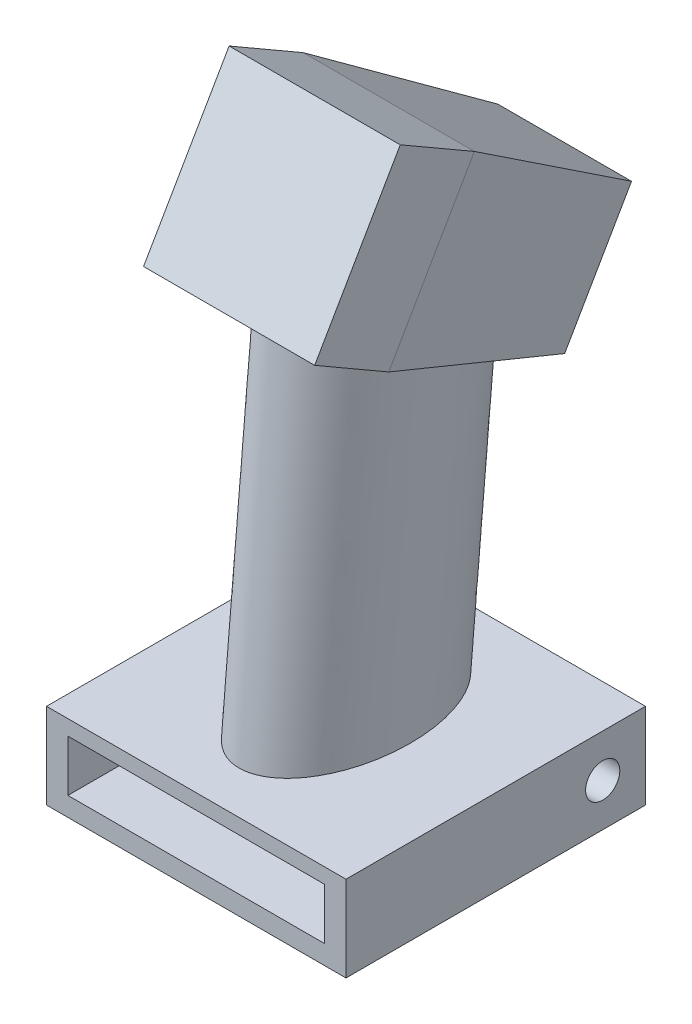
SolidWorks part; units mm, degrees
ref_plane "Front Plane" through (0, 0, 0) normal (0, 0, 1) x (1, 0, 0)
ref_plane "Top Plane" through (0, 0, 0) normal (0, 1, 0) x (1, 0, 0)
ref_plane "Right Plane" through (0, 0, 0) normal (1, 0, 0) x (0, 0, -1)
sketch "Sketch2" plane through (0, 0, 0) normal (0, 1, 0) x (1, 0, 0)
  line L0 (0, 0) -> (0, 35.7242) construction
  line L1 (0, 0) -> (12.5, 0) construction
  ellipse E0 centre (0, 0) end of major axis (0, -25) minor radius 15
  ellipse E1 centre (0, 0) end of major axis (0, 22.5) minor radius 12.5
  dimension "D1" = 12.5
  dimension "D2" = 15
  dimension "D3" = 22.5
  dimension "D4" = 25
sketch "Sketch3" plane through (0, 0, 0) normal (1, 0, 0) x (0, 0, -1)
  line L0 (0, 0) -> (5.118, 58.4992) construction
  line L1 (25, 0) -> (-25, 0) construction
  dimension "D1" = 85
extrude "Boss-Extrude1" add sketch "Sketch2" along direction (0, 0.9962, -0.0872) on the side of the normal blind 100
ref_axis "Axis1" through (0, 156.9007, 0) along (0, -1, 0)
ref_plane "Plane3" through (0, 100, 0) normal (0, 1, 0) x (1, 0, 0)
ref_axis "Axis4" through (16.5, 100, 0) along (-1, 0, 0)
ref_plane "Plane4" through (0, 25, 43.3013) normal (0, -0.5, -0.866) x (-1, 0, 0)
sketch "Sketch8" plane through (0, 25, 43.3013) normal (0, -0.5, -0.866) x (-1, 0, 0)
  line L0 (0, 135.88) -> (0, -6.4705) construction
  line L1 (-20, 66.6025) -> (20, 66.6025)
  line L2 (-20, 66.6025) -> (-20, 106.6025)
  line L3 (-20, 106.6025) -> (20, 106.6025)
  line L4 (20, 66.6025) -> (20, 106.6025)
  line L5 (-20, 66.6025) -> (20, 106.6025) construction
  line L6 (-20, 106.6025) -> (20, 66.6025) construction
  line L7 (-16.5, 86.6025) -> (16.5, 86.6025) construction
  point P0 (0, 86.6025)
  dimension "D1" = 40
  dimension "D2" = 40
extrude "Boss-Extrude2" add sketch "Sketch8" against normal blind 20 and the other way blind 50 draft 5 contours L1 L4 L3 L2
sketch "Sketch9" plane through (0, 0, 0) normal (0, -1, 0) x (-1, 0, 0)
  line L1 (35, 35) -> (-35, 35)
  line L2 (35, 35) -> (35, -35)
  line L3 (35, -35) -> (-35, -35)
  line L4 (-35, 35) -> (-35, -35)
  line L5 (35, 35) -> (-35, -35) construction
  line L6 (35, -35) -> (-35, 35) construction
  point P0 (0, 0)
  dimension "D1" = 70
  dimension "D2" = 70
extrude "Boss-Extrude3" add sketch "Sketch9" along normal blind 20
sketch "Sketch10" plane through (0, 0, 35) normal (0, 0, 1) x (1, 0, 0)
  line L0 (0, -9.5378) -> (0, 1.6534) construction
  line L1 (-30, -15.5378) -> (30, -15.5378)
  line L2 (-30, -15.5378) -> (-30, -3.5378)
  line L3 (-30, -3.5378) -> (30, -3.5378)
  line L4 (30, -15.5378) -> (30, -3.5378)
  line L5 (-30, -15.5378) -> (30, -3.5378) construction
  line L6 (-30, -3.5378) -> (30, -15.5378) construction
  line L7 (0, 0) -> (0, 58.4992) construction
  line L8 (0, -9.5378) -> (18.1969, -9.5378) construction
  point P0 (0, -9.5378)
  dimension "D1" = 12
  dimension "D2" = 60
extrude "Cut-Extrude1" cut sketch "Sketch10" against normal blind 55
sketch "Sketch11" plane through (35, 0, 0) normal (1, 0, 0) x (0, 0, -1)
  line L0 (35, -10) -> (58.9727, -10) construction
  line L2 (35, -20) -> (35, 0) construction
  circle A0 centre (25, -10) radius 1.75
  dimension "D2" = 3.5
  dimension "D1" = 10
extrude "Cut-Extrude2" cut sketch "Sketch11" against normal through all both and the other way through all
sketch "Sketch13" plane through (-35, 0, 0) normal (-1, 0, 0) x (0, 0, 1)
  circle A0 centre (-25, -10) radius 4
  dimension "D1" = 8
extrude "Cut-Extrude3" cut sketch "Sketch13" against normal blind 5
sketch "Sketch14" plane through (35, 0, 0) normal (1, 0, 0) x (0, 0, -1)
  circle A0 centre (25, -10) radius 4
  dimension "D1" = 8
extrude "Cut-Extrude4" cut sketch "Sketch14" against normal blind 10
